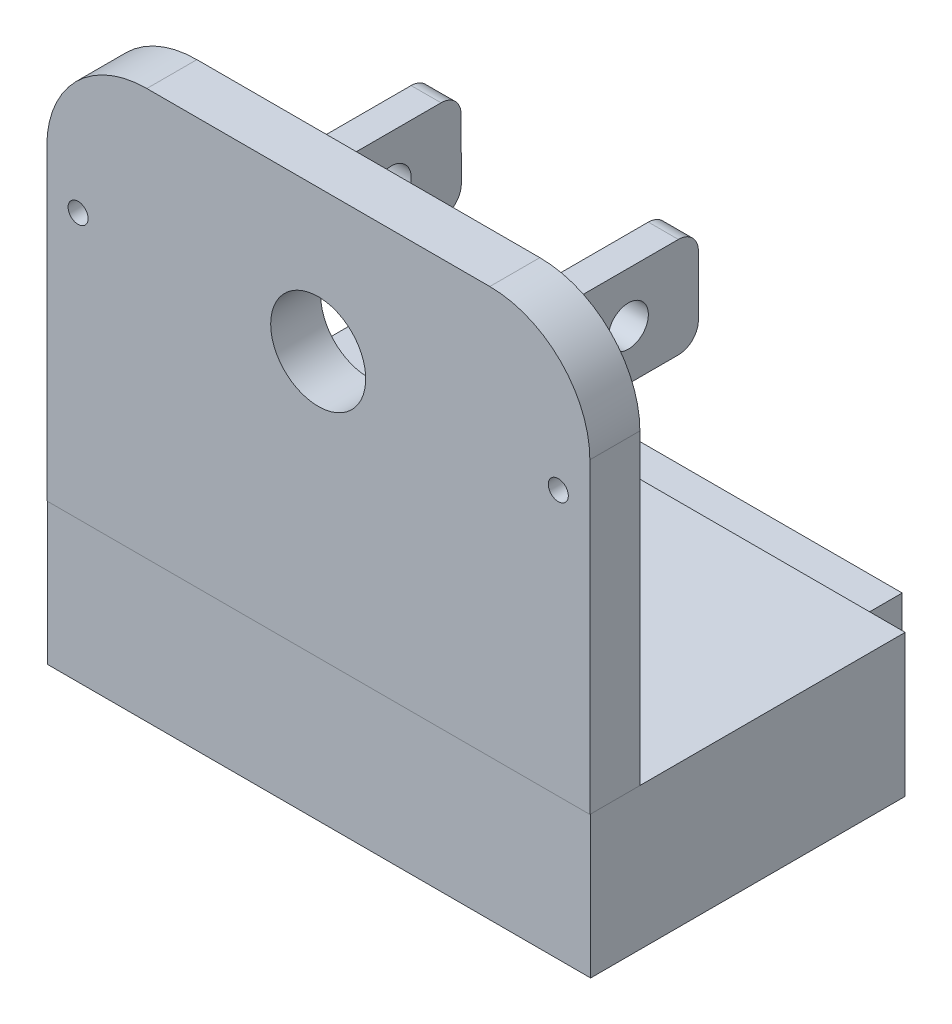
SolidWorks part; units mm, degrees
ref_plane "Front Plane" through (0, 0, 0) normal (0, 0, 1) x (1, 0, 0)
ref_plane "Top Plane" through (0, 0, 0) normal (0, 1, 0) x (1, 0, 0)
ref_plane "Right Plane" through (0, 0, 0) normal (1, 0, 0) x (0, 0, -1)
sketch "Sketch1" plane through (0, 0, 0) normal (0, 1, 0) x (1, 0, 0)
  line L1 (27.15, 8.545) -> (-27.15, 8.545)
  line L2 (27.15, 8.545) -> (27.15, -22.897)
  line L3 (27.15, -22.897) -> (-27.15, -22.897)
  line L4 (-27.15, 8.545) -> (-27.15, -22.897)
  point P0 (0, 0)
  dimension "D1" = 54.3
extrude "Boss-Extrude1" add sketch "Sketch1" along normal blind 11 and the other way blind 3.2
sketch "Sketch2" plane through (0, 0, -8.545) normal (0, 0, -1) x (-1, 0, 0)
  line L0 (-27.15, -3.2) -> (27.15, -3.2) construction
  line L1 (-17.15, 4.5571) -> (17.15, 4.5571)
  line L2 (-17.15, 4.5571) -> (-17.15, 1.044)
  line L3 (-17.15, 1.044) -> (17.15, 1.044)
  line L4 (17.15, 4.5571) -> (17.15, 1.044)
  line L5 (-27.15, 11) -> (-27.15, -3.2) construction
  line L6 (27.15, 11) -> (27.15, -3.2) construction
  line L7 (0, 4.5571) -> (0, 11)
  line L8 (-27.15, 11) -> (27.15, 11) construction
  point P0 (0, 8)
  point P7 (0, -3.2)
  dimension "D1" = 10
  dimension "D2" = 10
extrude "Boss-Extrude2" add sketch "Sketch2" along normal blind 9.7 contours L4 L1 L2 L3 region at (0, 2.8005, -8.545)
sketch "Sketch3" plane through (0, 11, 0) normal (0, 1, 0) x (1, 0, 0)
  line L1 (27.1542, -17.9782) -> (-27.1273, -17.9782)
  line L2 (27.1542, -17.9782) -> (27.1542, -22.9782)
  line L3 (27.1542, -22.9782) -> (-27.1273, -22.9782)
  line L4 (-27.1273, -17.9782) -> (-27.1273, -22.9782)
extrude "Boss-Extrude3" add sketch "Sketch3" along normal blind 40.7
sketch "Sketch4" plane through (0, 0, 22.897) normal (0, 0, 1) x (1, 0, 0)
  line L0 (0, -3.2) -> (0, 37.5)
  line L1 (-27.15, -3.2) -> (27.15, -3.2) construction
  line L7 (0, 37.5) -> (0, 25.3)
  circle A0 centre (0, 37.5) radius 4.75
  circle A5 centre (-24, 37.5) radius 1
  circle A6 centre (24, 37.5) radius 1
  dimension "D1" = 24
fillet "Fillet1" radius 10 2 edges at (-27.1273, 51.7, 20.4782) (27.1542, 51.7, 20.4782)
sketch "Sketch5" plane through (0, 0, 0) normal (0, 1, 0) x (1, 0, 0)
  line L0 (27.15, -17.9782) -> (27.15, 8.545) construction
  line L1 (13.65, -1.455) -> (15.65, -1.455)
  line L2 (13.65, -1.455) -> (13.65, -9.455)
  line L3 (13.65, -9.455) -> (15.65, -9.455)
  line L4 (15.65, -1.455) -> (15.65, -9.455)
  line L5 (17.15, 8.545) -> (-17.15, 8.545) construction
  line L7 (-27.15, 8.545) -> (-27.15, -22.897) construction
  line L8 (-13.65, -1.455) -> (-15.65, -1.455)
  line L9 (-13.65, -1.455) -> (-13.65, -9.455)
  line L10 (-13.65, -9.455) -> (-15.65, -9.455)
  line L11 (-15.65, -1.455) -> (-15.65, -9.455)
  line L12 (27.15, 8.545) -> (-27.15, 8.545) construction
  point P14 (-14.65, -9.455)
  dimension "D1" = 2
  dimension "D2" = 10
  dimension "D3" = 11.5
  dimension "D4" = 11.5
  dimension "D5" = 8
  dimension "D6" = 10
  dimension "D7" = 2
extrude "Cut-Extrude2" cut sketch "Sketch4" against normal blind 46 and the other way blind 21 contours A6 | A5 | A0
sketch "Sketch11" plane through (0, 0, 17.9782) normal (0, 0, -1) x (-1, 0, 0)
  line L0 (-17.1542, 51.7) -> (17.1273, 51.7) construction
  line L1 (-13, 42.2) -> (-10, 42.2)
  line L2 (-13, 42.2) -> (-13, 32.2)
  line L3 (-13, 32.2) -> (-10, 32.2)
  line L4 (-10, 42.2) -> (-10, 32.2)
  line L6 (13.6875, 32.1604) -> (10.6875, 32.1693)
  line L7 (0.3728, 51.7376) -> (0.3123, 10.9591) construction
  line L8 (13.7172, 42.1604) -> (10.7172, 42.1693)
  line L9 (13.7172, 42.1604) -> (13.6875, 32.1604)
  line L10 (10.7172, 42.1693) -> (10.6875, 32.1693)
  circle A0 centre (0, 37.5) radius 4.75 construction
  dimension "D3" = 10
  dimension "D1" = 9.5
extrude "Boss-Extrude4" add sketch "Sketch11" along normal blind 20
extrude "Boss-Extrude5" add sketch "Sketch11<2>" along normal blind 10
sketch "Sketch11<2>" plane through (0, 0, 17.9782) normal (0, 0, -1) x (-1, 0, 0) same geometry as "Sketch11"
sketch "Sketch12" plane through (13, 0, 0) normal (1, 0, 0) x (0, 0, -1)
  line L3 (2.0218, 42.2) -> (2.0218, 32.2) construction
  line L4 (2.0218, 42.2) -> (-17.9782, 42.2) construction
  circle A0 centre (-4.9782, 37.2) radius 2
  point P2 (-35.6451, 39.9857)
  point P3 (0, 0)
  point P4 (-12.6025, 37.2634)
  point P5 (0, 0)
  dimension "D1" = 7
  dimension "D2" = 5
extrude "Cut-Extrude3" cut sketch "Sketch12" against normal blind 36
fillet "Fillet2" radius 2 4 edges at (-12.1875, 32.1649, -2.0218) (-12.2172, 42.1648, -2.0218) (11.5, 32.2, -2.0218) (11.5, 42.2, -2.0218)
